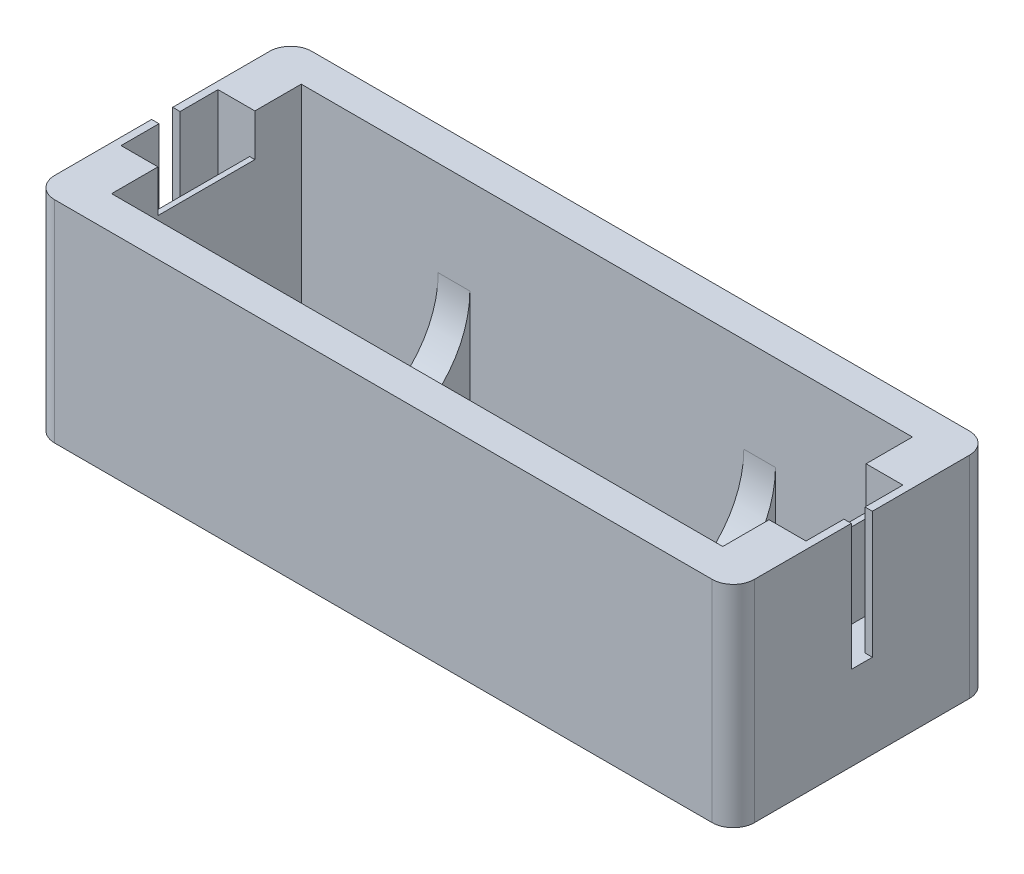
SolidWorks part; units mm, degrees
ref_plane "Front Plane" through (0, 0, 0) normal (0, 0, 1) x (1, 0, 0)
ref_plane "Top Plane" through (0, 0, 0) normal (0, 1, 0) x (1, 0, 0)
ref_plane "Right Plane" through (0, 0, 0) normal (1, 0, 0) x (0, 0, -1)
sketch "Sketch2" plane through (0, 0, 0) normal (0, 1, 0) x (1, 0, 0)
  line L1 (-33.2, -12.2) -> (33.2, -12.2)
  line L2 (-33.2, -12.2) -> (-33.2, 12.2)
  line L3 (-33.2, 12.2) -> (33.2, 12.2)
  line L4 (33.2, -12.2) -> (33.2, 12.2)
  line L5 (-33.2, -12.2) -> (33.2, 12.2) construction
  line L6 (-33.2, 12.2) -> (33.2, -12.2) construction
  point P0 (0, 0)
  dimension "D1" = 66.4
  dimension "D2" = 24.4
extrude "Boss-Extrude1" add sketch "Sketch2" along normal blind 20
sketch "Sketch3" plane through (0, 20, 0) normal (0, 1, 0) x (1, 0, 0)
  line L0 (33.2, -12.2) -> (33.2, 12.2) construction
  line L1 (-29, 9) -> (29, 9)
  line L2 (-29, 9) -> (-29, -9)
  line L3 (-29, -9) -> (29, -9)
  line L4 (29, 9) -> (29, -9)
  line L5 (-29, 9) -> (29, -9) construction
  line L6 (-29, -9) -> (29, 9) construction
  line L7 (-33.2, -12.2) -> (33.2, -12.2) construction
  point P0 (0, 0)
  dimension "D1" = 4.2
  dimension "D2" = 3.2
extrude "Cut-Extrude1" cut sketch "Sketch3" against normal offset from surface (18 mm away) 2 up to face at (0, 0, 0)
fillet "Fillet1" radius 2 4 edges at (-33.2, 10, -12.2) (33.2, 10, -12.2) (33.2, 10, 12.2) (-33.2, 10, 12.2)
sketch "Sketch4" plane through (0, 20, 0) normal (0, 1, 0) x (1, 0, 0)
  line L0 (-29, 9) -> (-29, -9) construction
  line L1 (-29, 0) -> (-29.5, 0)
  line L2 (-29, 0) -> (-29, 4.6)
  line L3 (-29, 4.6) -> (-29.5, 4.6)
  line L4 (-29.5, 0) -> (-29.5, 4.6)
  dimension "D1" = 0.5
  dimension "D2" = 4.6
extrude "Cut-Extrude2" cut sketch "Sketch4" against normal offset from surface (4 mm away) 4 up to face at (0, 20, 0)
sketch "Sketch5" plane through (0, 20, 0) normal (0, 1, 0) x (1, 0, 0)
  line L1 (-29.5, 0) -> (-32.5, 0)
  line L2 (-29.5, 0) -> (-29.5, 4.6)
  line L3 (-29.5, 4.6) -> (-32.5, 4.6)
  line L4 (-32.5, 0) -> (-32.5, 4.6)
  dimension "D2" = 4.6
extrude "Cut-Extrude3" cut sketch "Sketch5" against normal offset from surface (12 mm away) 12 up to face at (-14.625, 20, -1.15)
mirror "Mirror4" about plane through (0, 0, 0) normal (1, 0, 0) of "Cut-Extrude3", "Cut-Extrude2"
mirror "Mirror5" about plane through (0, 0, 0) normal (0, 0, 1) of "Mirror4"
sketch "Sketch6" plane through (33.2, 0, 0) normal (1, 0, 0) x (0, 0, -1)
  line L0 (-10.2, 0) -> (10.2, 0) construction
  circle A0 centre (0, 12) radius 0.75
  dimension "D1" = 1.5
  dimension "D2" = 12
ref_plane "Plane1" through (-14.5, 0, 0) normal (1, 0, 0) x (0, 0, -1)
sketch "Sketch7" plane through (-14.5, 0, 0) normal (1, 0, 0) x (0, 0, -1)
  line L0 (-9, 2) -> (9, 2) construction
  line L1 (-9, 2) -> (-9, 20) construction
  line L2 (9, 2) -> (9, 20) construction
  circle A0 centre (0, 11) radius 9
sketch "Sketch8" plane through (0, 2, 0) normal (0, 1, 0) x (1, 0, 0)
  line L0 (-14.5, -9) -> (-14.5, 9) construction
  line L1 (-16, -9) -> (-13, -9)
  line L2 (-16, -9) -> (-16, 9)
  line L3 (-16, 9) -> (-13, 9)
  line L4 (-13, -9) -> (-13, 9)
  line L5 (-16, -9) -> (-13, 9) construction
  line L6 (-16, 9) -> (-13, -9) construction
  line L7 (29, 9) -> (-29, 9) construction
  point P0 (-14.5, 0)
  dimension "D1" = 3
extrude "Boss-Extrude2" add sketch "Sketch8" along normal blind 9
extrude "Cut-Extrude5" cut sketch "Sketch7" against normal up to next and the other way up to next
mirror "Mirror7" about plane through (0, 0, 0) normal (1, 0, 0) of "Cut-Extrude5", "Boss-Extrude2"
sketch "Sketch9" plane through (0, 20, 0) normal (0, 1, 0) x (1, 0, 0)
  line L0 (-33.2, 10.2) -> (-33.2, -10.2) construction
  line L1 (-32.5, 0) -> (-33.2, 0)
  line L2 (-32.5, 0) -> (-32.5, 1)
  line L3 (-32.5, 1) -> (-33.2, 1)
  line L4 (-33.2, 0) -> (-33.2, 1)
extrude "Cut-Extrude6" cut sketch "Sketch9" against normal up to surface (12 mm away) up to face at (-31, 8, 0)
mirror "Mirror8" about plane through (0, 0, 0) normal (1, 0, 0) of "Cut-Extrude6" second plane through (0, 0, 0) second plane normal (0, 0, 1)
equation "\"D1@Sketch2\" = 50 + 6.4 + 10"
equation "\"D2@Sketch2\" = 14 + 6.4 + 4"
equation "\"D1@Boss-Extrude1\"= 14 + 2 + 4"
equation "\"D1@Sketch3\"=4.2"
equation "\"D2@Sketch3\"=3.2"
equation "\"D1@Cut-Extrude1\"=2"
equation "\"D1@Fillet1\"=2"
equation "\"D2@Sketch4\"=4.6"
equation "\"D1@Sketch5\"=3"
equation "\"D2@Sketch5\"=4.6"
equation "\"D2@Sketch6\"=12"
equation "\"D1@Sketch9\"=1"
